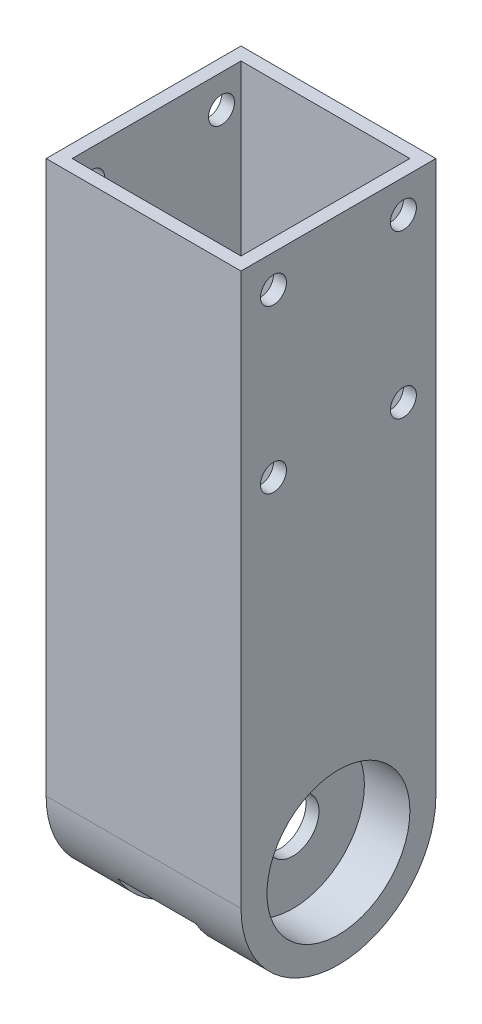
SolidWorks part; units mm, degrees
ref_plane "Front Plane" through (0, 0, 0) normal (0, 0, 1) x (1, 0, 0)
ref_plane "Top Plane" through (0, 0, 0) normal (0, 1, 0) x (1, 0, 0)
ref_plane "Right Plane" through (0, 0, 0) normal (1, 0, 0) x (0, 0, -1)
sketch "Sketch1" plane through (0, 0, 0) normal (0, 1, 0) x (1, 0, 0)
  line L1 (-15, -15) -> (15, -15)
  line L2 (-15, -15) -> (-15, 15)
  line L3 (-15, 15) -> (15, 15)
  line L4 (15, -15) -> (15, 15)
  line L5 (-15, -15) -> (15, 15) construction
  line L6 (-15, 15) -> (15, -15) construction
  line L11 (-6, -6) -> (6, 6) construction
  line L12 (-6, 6) -> (6, -6) construction
  line L13 (-6, -13) -> (6, -13)
  line L14 (-6, -13) -> (-6, 13)
  line L15 (-6, 13) -> (6, 13)
  line L16 (6, -13) -> (6, 13)
  line L17 (-6, -13) -> (6, 13) construction
  line L18 (-6, 13) -> (6, -13) construction
  point P0 (0, 0)
  point P6 (0, 0)
  point P11 (0, 0)
  dimension "D1" = 30
  dimension "D2" = 30
  dimension "D3" = 9
  dimension "D4" = 2
extrude "Boss-Extrude2" add sketch "Sketch1" along normal blind 100
sketch "Sketch2" plane through (15, 0, 0) normal (1, 0, 0) x (0, 0, -1)
  line L0 (-15, 95) -> (15, 95)
  line L1 (-15, 100) -> (-15, 0) construction
  line L2 (15, 100) -> (15, 0) construction
  line L3 (-15, 100) -> (15, 100) construction
  line L4 (-15, 100) -> (-15, 70) construction
  line L5 (-15, 70) -> (15, 70) construction
  circle A0 centre (-10, 95) radius 2
  circle A1 centre (10, 95) radius 2
  circle A2 centre (-10, 70) radius 2
  circle A3 centre (10, 70) radius 2
  dimension "D2" = 4
  dimension "D4" = 4
  dimension "D7" = 4
  dimension "D8" = 4
  dimension "D1" = 5
  dimension "D3" = 5
  dimension "D5" = 5
  dimension "D6" = 30
extrude "Cut-Extrude1" cut sketch "Sketch2" against normal blind 51 contours A1 | A3 | A0 | A2
sketch "Sketch3" plane through (0, 100, 0) normal (0, 1, 0) x (1, 0, 0)
  line L0 (-6, 13) -> (-13, 13)
  line L1 (-15, 15) -> (-15, -15) construction
  line L2 (-13, 13) -> (-13, -13)
  line L7 (-6, -13) -> (-13, -13)
  line L8 (-6, 13) -> (-6, -13)
  line L10 (6, 13) -> (13, 13)
  line L11 (6, 13) -> (6, -13)
  line L12 (6, -13) -> (13, -13)
  line L13 (13, 13) -> (13, -13)
  dimension "D1" = 2
  dimension "D2" = 2
extrude "Cut-Extrude2" cut sketch "Sketch3" against normal blind 70
fillet "Fillet1" radius 15 2 edges at (0, 0, -15) (0, 0, 15)
sketch "Sketch5" plane through (15, 0, 0) normal (1, 0, 0) x (0, 0, -1)
  circle A0 centre (0, 15) radius 4
  dimension "D1" = 8
extrude "Cut-Extrude3" cut sketch "Sketch5" against normal blind 50
sketch "Sketch6" plane through (15, 0, 0) normal (1, 0, 0) x (0, 0, -1)
  circle A0 centre (0, 15) radius 11
  dimension "D1" = 22
extrude "Cut-Extrude4" cut sketch "Sketch6" against normal blind 7
sketch "Sketch7" plane through (-15, 0, 0) normal (-1, 0, 0) x (0, 0, 1)
  circle A0 centre (0, 15) radius 11
  dimension "D1" = 22
extrude "Cut-Extrude5" cut sketch "Sketch7" against normal blind 7
